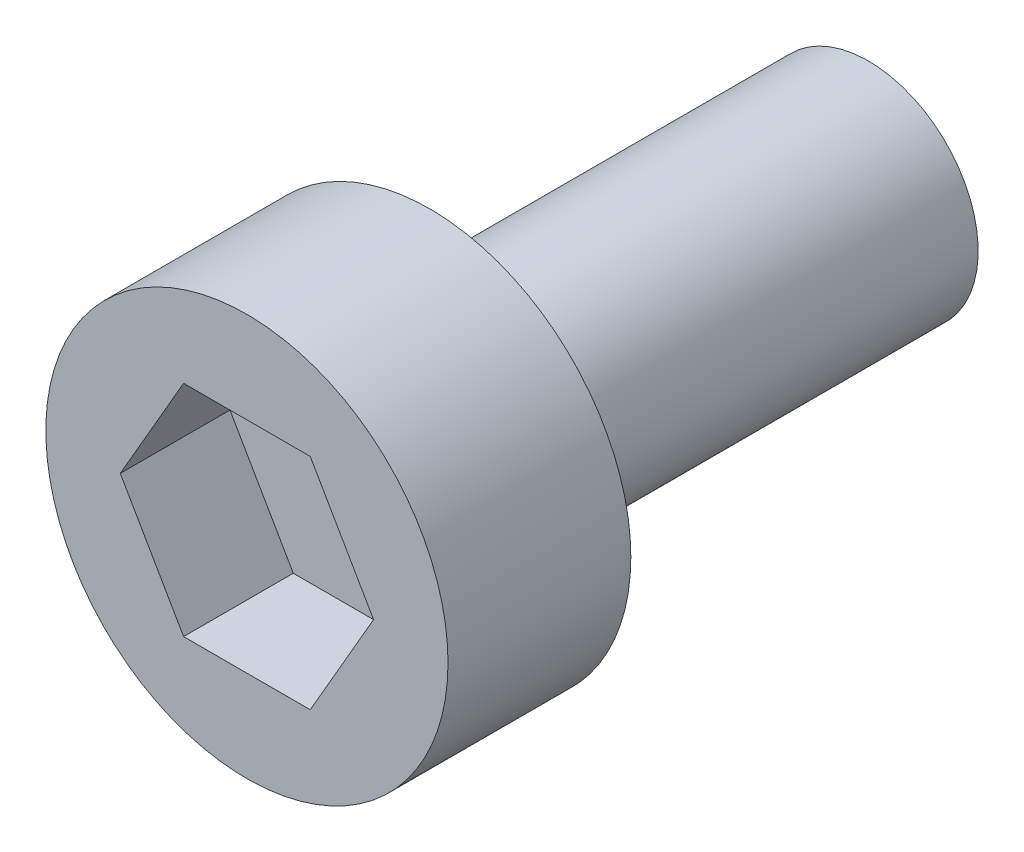
SolidWorks part; units mm, degrees
ref_plane "前视基准面" through (0, 0, 0) normal (0, 0, 1) x (1, 0, 0)
ref_plane "上视基准面" through (0, 0, 0) normal (0, 1, 0) x (1, 0, 0)
ref_plane "右视基准面" through (0, 0, 0) normal (1, 0, 0) x (0, 0, -1)
sketch "草图1" plane through (0, 0, 0) normal (0, 0, 1) x (1, 0, 0)
  line L1 (1.7321, 0) -> (0.866, 1.5)
  line L2 (0.866, 1.5) -> (-0.866, 1.5)
  line L3 (-0.866, 1.5) -> (-1.7321, 0)
  line L4 (-1.7321, 0) -> (-0.866, -1.5)
  line L5 (-0.866, -1.5) -> (0.866, -1.5)
  line L6 (0.866, -1.5) -> (1.7321, 0)
  circle A0 centre (0, 0) radius 2.75
  circle A1 centre (0, 0) radius 1.5 construction
  dimension "D1" = 5.5
  dimension "D2" = 3
extrude "凸台-拉伸1" add sketch "草图1" along normal blind 2.5
sketch "草图2" plane through (0, 0, 0) normal (0, 0, -1) x (-1, 0, 0)
  circle A0 centre (0, 0) radius 1.5
  dimension "D1" = 3
extrude "凸台-拉伸2" add sketch "草图2" along normal blind 6
extrude "凸台-拉伸3" add sketch "草图1<3>" along normal blind 1 from surface contours L5 L6 L1 L2 L3 L4 region at (0, 0, 0) starting at face at (2.75, 0, 0)
sketch "草图1<3>" plane through (0, 0, 0) normal (0, 0, 1) x (1, 0, 0) same geometry as "草图1"
